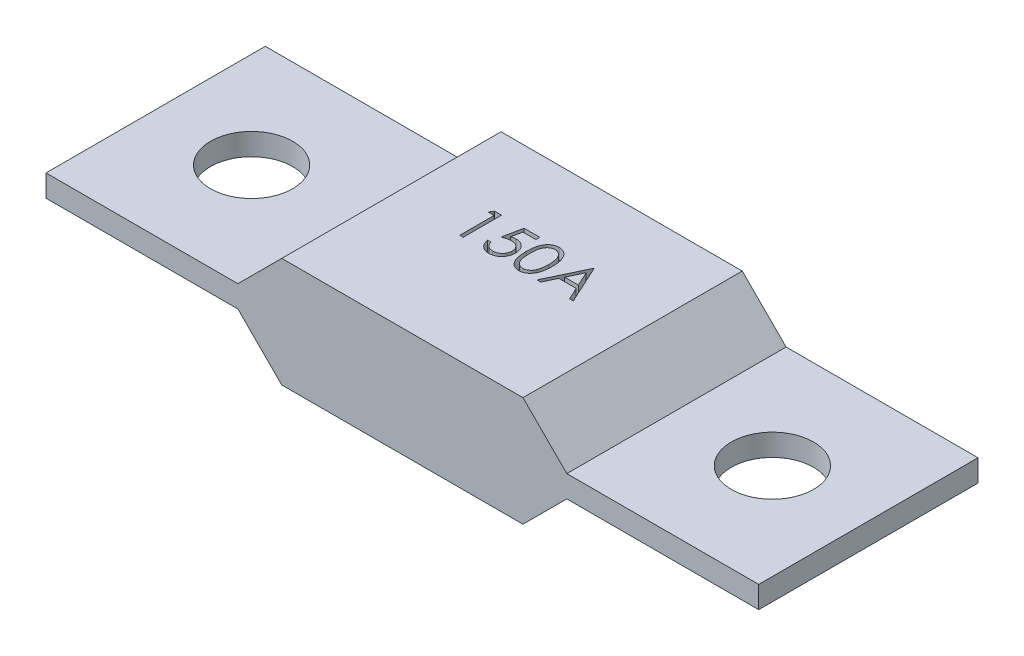
SolidWorks part; units mm, degrees
ref_plane "Front Plane" through (0, 0, 0) normal (0, 0, 1) x (1, 0, 0)
ref_plane "Top Plane" through (0, 0, 0) normal (0, 1, 0) x (1, 0, 0)
ref_plane "Right Plane" through (0, 0, 0) normal (1, 0, 0) x (0, 0, -1)
sketch "Sketch1" plane through (0, 0, 0) normal (0, 1, 0) x (1, 0, 0)
  line L0 (23.75, 33.349) -> (23.75, -31.4534) construction
  line L1 (-8.75, -10) -> (8.75, -10)
  line L2 (-8.75, -10) -> (-8.75, 10)
  line L3 (-8.75, 10) -> (8.75, 10)
  line L4 (8.75, -10) -> (8.75, 10)
  line L5 (38.75, -10) -> (38.75, 10)
  line L6 (56.25, 10) -> (38.75, 10)
  line L7 (56.25, -10) -> (56.25, 10)
  line L8 (56.25, -10) -> (38.75, -10)
  circle A0 centre (0, 0) radius 3.75
  circle A1 centre (47.5, 0) radius 3.75
  dimension "D3" = 7.5
  dimension "D1" = 17.5
  dimension "D2" = 20
  dimension "D4" = 10
  dimension "D5" = 8.75
  dimension "D6" = 15
extrude "Boss-Extrude1" add sketch "Sketch1" along normal blind 2
sketch "Sketch2" plane through (8.75, 0, 0) normal (1, 0, 0) x (0, 0, -1)
  line L0 (-10, 2) -> (10, 2) construction
  line L1 (-10, -4) -> (10, -4)
  line L2 (-10, -4) -> (-10, 6)
  line L3 (-10, 6) -> (10, 6)
  line L4 (10, -4) -> (10, 6)
  point P4 (-10, 5.8755)
  point P5 (10, 6.2159)
  dimension "D1" = 10
  dimension "D2" = 4
extrude "Boss-Extrude2" add sketch "Sketch2" along normal up to surface (30 mm away) up to face at (38.75, 1, 0)
chamfer "Chamfer1" distance 4 angle 45 4 edges at (38.75, -4, 0) (38.75, 6, 0) (8.75, -4, 0) (8.75, 6, 0)
sketch "Sketch3" plane through (0, 6, 0) normal (0, 1, 0) x (1, 0, 0)
  text T0 "150A"
extrude "Cut-Extrude1" cut sketch "Sketch3" against normal blind 1
